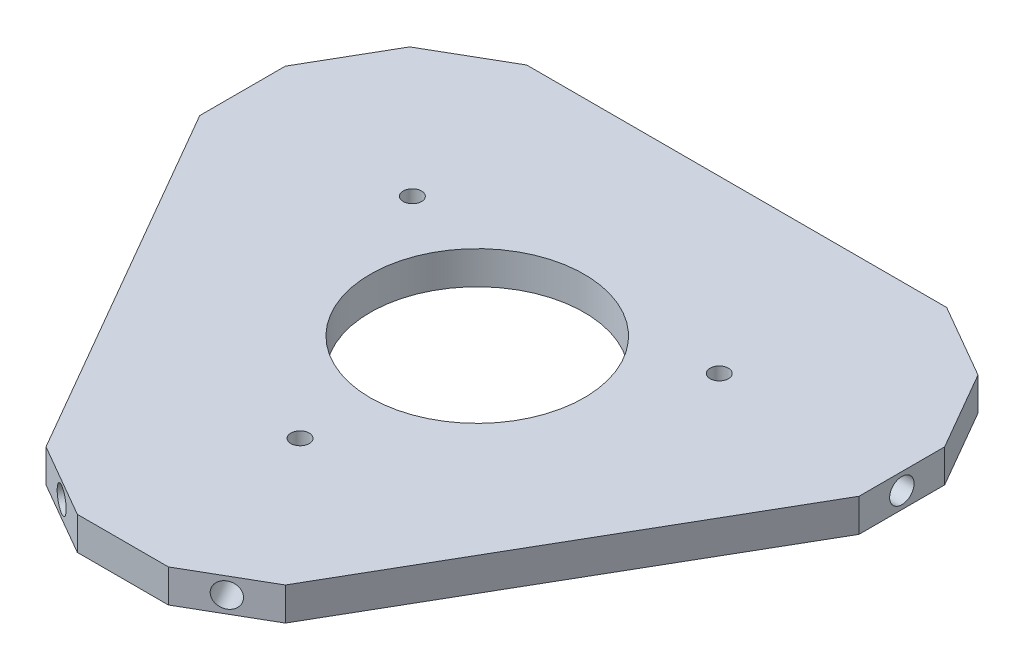
SolidWorks part; units mm, degrees
material "Prusament PETG"
ref_plane "Front Plane" through (0, 0, 0) normal (0, 0, 1) x (1, 0, 0)
ref_plane "Top Plane" through (0, 0, 0) normal (0, 1, 0) x (1, 0, 0)
ref_plane "Right Plane" through (0, 0, 0) normal (1, 0, 0) x (0, 0, -1)
sketch "Sketch1" plane through (0, 0, 0) normal (0, 1, 0) x (1, 0, 0)
  line L19 (-181.6084, -39.9863) -> (-139.182, -113.471)
  line L22 (-181.6084, -39.9863) -> (-166.0793, -13.089)
  line L27 (-166.0793, -13.089) -> (-81.2265, -13.089)
  line L28 (-81.2265, -13.089) -> (-65.6973, -39.9863)
  line L29 (-65.6973, -39.9863) -> (-108.1237, -113.471)
  line L30 (-108.1237, -113.471) -> (-139.182, -113.471)
  circle A5 centre (-123.6529, -55.5154) radius 60 construction
  dimension "D1" = 120
  dimension "D5" = 31.0583
  dimension "D2" = 30
  dimension "D4" = 90
extrude "Boss-Extrude2" add sketch "Sketch1" along normal blind 5.4 contours L29 L28 L27 L22 L19 L30
fillet "Chamfer3" radius 14 1 edges at (-139.182, 2.7, 113.471) profile chamfer
fillet "Chamfer4" radius 14 1 edges at (-108.1237, 2.7, 113.471) profile chamfer
fillet "Chamfer5" radius 14 1 edges at (-65.6973, 2.7, 39.9863) profile chamfer
fillet "Chamfer6" radius 14 1 edges at (-81.2265, 2.7, 13.089) profile chamfer
fillet "Chamfer7" radius 14 1 edges at (-166.0793, 2.7, 13.089) profile chamfer
fillet "Chamfer8" radius 14 1 edges at (-181.6084, 2.7, 39.9863) profile chamfer
sketch "Sketch7" plane through (-81.9091, 0, 141.8708) normal (-0.5, 0, 0.866) x (0.866, 0, 0.5)
  line L0 (-63.7997, 2.7) -> (-63.7997, 0) construction
  line L1 (-56.7997, 0) -> (-70.7997, 0) construction
  line L3 (-70.7997, 5.4) -> (-56.7997, 5.4) construction
  point P0 (-63.7997, 2.7)
  dimension "D1" = 2.7
hole_wizard "Ø3.0mm Dowel Hole1" positions "Sketch7" profile "Sketch6" hole size "Ø3.0" standard "DIN"
sketch "Sketch6" plane through (-137.1613, 2.7, 109.971) normal (0, 1, 0) x (0.866, 0, 0.5)
  line L0 (0, 0) -> (0, 11.2017)
  line L1 (0, 11.2017) -> (2, 10)
  line L2 (2, 10) -> (2, 0)
  line L5 (2, 0) -> (0, 0)
  line L10 (0, 11.2017) -> (-2, 10) construction
  line L11 (0, -6.35) -> (0, 107.95) construction
  dimension "Hole Dia." = 4
  dimension "Hole Depth" = 10
  dimension "Drill Angle" = 118
sketch "Sketch10" plane through (20.0827, 0, 34.7843) normal (0.5, 0, 0.866) x (0.866, 0, -0.5)
  line L0 (-150.3734, 2.7) -> (-150.3734, 0) construction
  line L1 (-143.3734, 0) -> (-157.3734, 0) construction
  line L2 (-157.3734, 5.4) -> (-143.3734, 5.4) construction
  point P0 (-150.3734, 2.7)
  dimension "D1" = 2.7
hole_wizard "Ø3.0mm Dowel Hole2" positions "Sketch10" profile "Sketch9" hole size "Ø3.0" standard "DIN"
sketch "Sketch9" plane through (-110.1444, 2.7, 109.971) normal (0, 1, 0) x (0.866, 0, -0.5)
  line L0 (0, 0) -> (0, 11.2017)
  line L1 (0, 11.2017) -> (2, 10)
  line L2 (2, 10) -> (2, 0)
  line L5 (2, 0) -> (0, 0)
  line L10 (0, 11.2017) -> (-2, 10) construction
  line L11 (0, -6.35) -> (0, 107.95) construction
  dimension "Hole Dia." = 4
  dimension "Hole Depth" = 10
  dimension "Drill Angle" = 118
sketch "Sketch13" plane through (-69.7388, 0, 0) normal (1, 0, 0) x (0, 0, -1)
  line L0 (-39.9863, 2.7) -> (-39.9863, 0) construction
  line L1 (-32.9863, 0) -> (-46.9863, 0) construction
  line L3 (-46.9863, 5.4) -> (-32.9863, 5.4) construction
  point P0 (-39.9863, 2.7)
  dimension "D1" = 2.7
hole_wizard "Ø3.0mm Dowel Hole3" positions "Sketch13" profile "Sketch12" hole size "Ø3.0" standard "DIN"
sketch "Sketch12" plane through (-69.7388, 2.7, 39.9863) normal (0, 1, 0) x (0, 0, -1)
  line L0 (0, 0) -> (0, 11.2017)
  line L1 (0, 11.2017) -> (2, 10)
  line L2 (2, 10) -> (2, 0)
  line L5 (2, 0) -> (0, 0)
  line L10 (0, 11.2017) -> (-2, 10) construction
  line L11 (0, -6.35) -> (0, 107.95) construction
  dimension "Hole Dia." = 4
  dimension "Hole Depth" = 10
  dimension "Drill Angle" = 118
sketch "Sketch16" plane through (-27.995, 0, 48.4888) normal (0.5, 0, -0.866) x (-0.866, 0, -0.5)
  line L0 (63.7997, 2.7) -> (63.7997, 0) construction
  line L1 (70.7997, 0) -> (56.7997, 0) construction
  line L3 (56.7997, 5.4) -> (70.7997, 5.4) construction
  point P0 (63.7997, 2.7)
  dimension "D1" = 2.7
hole_wizard "Ø3.0mm Dowel Hole4" positions "Sketch16" profile "Sketch15" hole size "Ø3.0" standard "DIN"
sketch "Sketch15" plane through (-83.2472, 2.7, 16.589) normal (0, 1, 0) x (-0.866, 0, -0.5)
  line L0 (0, 0) -> (0, 11.2017)
  line L1 (0, 11.2017) -> (2, 10)
  line L2 (2, 10) -> (2, 0)
  line L5 (2, 0) -> (0, 0)
  line L10 (0, 11.2017) -> (-2, 10) construction
  line L11 (0, -6.35) -> (0, 107.95) construction
  dimension "Hole Dia." = 4
  dimension "Hole Depth" = 10
  dimension "Drill Angle" = 118
sketch "Sketch19" plane through (-33.8314, 0, -58.5977) normal (-0.5, 0, -0.866) x (-0.866, 0, 0.5)
  line L0 (150.3734, 2.7) -> (150.3734, 0) construction
  line L1 (157.3734, 0) -> (143.3734, 0) construction
  line L3 (143.3734, 5.4) -> (157.3734, 5.4) construction
  point P0 (150.3734, 2.7)
  dimension "D1" = 2.7
hole_wizard "Ø3.0mm Dowel Hole5" positions "Sketch19" profile "Sketch18" hole size "Ø3.0" standard "DIN"
sketch "Sketch18" plane through (-164.0585, 2.7, 16.589) normal (0, 1, 0) x (-0.866, 0, 0.5)
  line L0 (0, 0) -> (0, 11.2017)
  line L1 (0, 11.2017) -> (2, 10)
  line L2 (2, 10) -> (2, 0)
  line L5 (2, 0) -> (0, 0)
  line L10 (0, 11.2017) -> (-2, 10) construction
  line L11 (0, -6.35) -> (0, 107.95) construction
  dimension "Hole Dia." = 4
  dimension "Hole Depth" = 10
  dimension "Drill Angle" = 118
sketch "Sketch22" plane through (-177.567, 0, 0) normal (-1, 0, 0) x (0, 0, 1)
  line L0 (39.9863, 2.7) -> (39.9863, 0) construction
  line L1 (46.9863, 0) -> (32.9863, 0) construction
  line L3 (32.9863, 5.4) -> (46.9863, 5.4) construction
  point P0 (39.9863, 2.7)
  dimension "D1" = 2.7
hole_wizard "Ø3.0mm Dowel Hole6" positions "Sketch22" profile "Sketch21" hole size "Ø3.0" standard "DIN"
sketch "Sketch21" plane through (-177.567, 2.7, 39.9863) normal (0, 1, 0) x (0, 0, 1)
  line L0 (0, 0) -> (0, 11.2017)
  line L1 (0, 11.2017) -> (2, 10)
  line L2 (2, 10) -> (2, 0)
  line L5 (2, 0) -> (0, 0)
  line L10 (0, 11.2017) -> (-2, 10) construction
  line L11 (0, -6.35) -> (0, 107.95) construction
  dimension "Hole Dia." = 4
  dimension "Hole Depth" = 10
  dimension "Drill Angle" = 118
sketch "Sketch23" plane through (0, 5.4, 0) normal (0, 1, 0) x (1, 0, 0)
  circle A0 centre (-123.6529, -55.5154) radius 17.5
  dimension "D1" = 35
extrude "Cut-Extrude1" cut sketch "Sketch23" against normal through all
sketch "Sketch24" plane through (0, 5.4, 0) normal (0, 1, 0) x (1, 0, 0)
  line L0 (-123.6529, -55.5154) -> (-123.6529, -113.471) construction
  line L1 (-116.2066, -113.471) -> (-131.0991, -113.471) construction
  line L2 (-123.6529, -55.5154) -> (-173.8438, -26.5376) construction
  line L3 (-177.567, -32.9863) -> (-170.1207, -20.089) construction
  line L4 (-123.6529, -55.5154) -> (-73.4619, -26.5376) construction
  line L5 (-77.185, -20.089) -> (-69.7388, -32.9863) construction
  circle A2 centre (-98.5574, -41.0265) radius 1.5
  circle A3 centre (-148.7484, -41.0265) radius 1.5
  circle A4 centre (-123.6529, -84.4932) radius 1.5
  point P17 (0, 0)
  point P20 (0, 0)
  point P21 (-123.6529, -84.4932)
  point P22 (0, 0)
  point P23 (-98.5574, -41.0265)
  point P24 (0, 0)
  point P25 (-148.7484, -41.0265)
extrude "Cut-Extrude2" cut sketch "Sketch24" against normal through all both and the other way through all
equation "\"Hexagon_long_side_length\"= 2 * \"Matlab_Diameter_enclosing_circle\" / 2 * sin ( \"theta_long_side\" / 2 )"
equation "\"Hexagon_short_side_length\"= 2 * \"Matlab_Diameter_enclosing_circle\" / 2 * sin ( \"theta_short_side\" / 2 )"
equation "\"Width_upper_lower_shell\"= 0.0054"
equation "\"D1@Boss-Extrude2\"=\"Width_upper_lower_shell\""
equation "\"holes_distance_from edge\"= \"Hexagon_short_side_length\" / 4m"
equation "\"holes_distance_from_eachother\"= 0.01"
equation "\"holes_distance_from_top\"= \"Width_upper_lower_shell\" / 2"
equation "\"Ditance_between_pair_of_holes\"= \"Hexagon_short_side_length\" - 2 * \"holes_distance_from edge\""
equation "\"theta_short_side\"= 30deg"
equation "\"theta_long_side\"= 120deg - \"theta_short_side\""
equation "\"Diametre_enclosing_circle\"= \"Matlab_Diameter_enclosing_circle\" * 0.75"
equation "\"Radius_enclosing_circle\"= \"Diametre_enclosing_circle\" / 2"
equation "\"Matlab_Diameter_enclosing_circle\"= 120mm"
equation "\"Distance_of_servo_centre_of_rotation_to_edge\"= 1.4cm"
equation "\"D1@Sketch1\"=\"Matlab_Diameter_enclosing_circle\""
equation "\"D2@Sketch1\" = \"theta_short_side\""
equation "\"D1@Sketch7\"=\"holes_distance_from_top\""
equation "\"D1@Sketch13\" = \"holes_distance_from_top\""
equation "\"D1@Sketch10\"=\"holes_distance_from_top\""
equation "\"D1@Sketch16\" = \"holes_distance_from_top\""
equation "\"D1@Sketch19\" = \"holes_distance_from_top\""
equation "\"D1@Sketch22\" = \"holes_distance_from_top\""
equation "\"Diameter_inner_hole\"= 0.035"
equation "\"D1@Sketch23\"=\"Diameter_inner_hole\""
